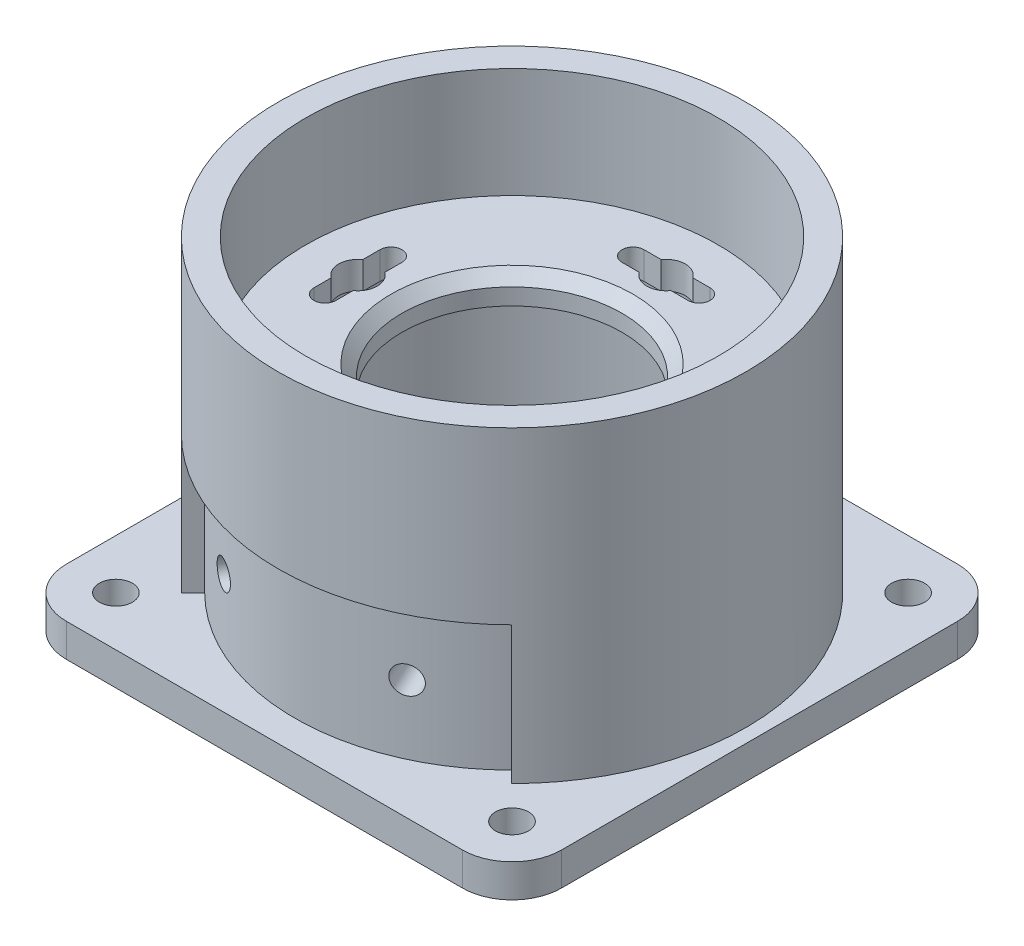
SolidWorks part; units mm, degrees
ref_plane "前视基准面" through (0, 0, 0) normal (0, 0, 1) x (1, 0, 0)
ref_plane "上视基准面" through (0, 0, 0) normal (0, 1, 0) x (1, 0, 0)
ref_plane "右视基准面" through (0, 0, 0) normal (1, 0, 0) x (0, 0, -1)
other "Configuration Table"
sketch "草图1" plane through (0, 0, 0) normal (0, 1, 0) x (1, 0, 0)
  line L0 (-27.9508, -25) -> (27.9508, -25)
  line L1 (-36, 45) -> (36, 45)
  line L2 (-45, 36) -> (-45, -36)
  line L3 (-36, -45) -> (36, -45)
  line L4 (45, 36) -> (45, -36)
  line L5 (-45, 45) -> (45, -45) construction
  line L6 (-45, -45) -> (45, 45) construction
  circle A0 centre (0, 0) radius 42.5
  circle A1 centre (0, 0) radius 37.5
  circle A2 centre (0, 0) radius 20
  arc A3 (36, 45) -> (45, 36) centre (36, 36) cw
  arc A4 (-45, -36) -> (-36, -45) centre (-36, -36) ccw
  arc A5 (-36, 45) -> (-45, 36) centre (-36, 36) ccw
  arc A6 (36, -45) -> (45, -36) centre (36, -36) ccw
  circle A7 centre (-36, 36) radius 3
  circle A8 centre (36, 36) radius 3
  circle A9 centre (36, -36) radius 3
  circle A10 centre (-36, -36) radius 3
  point P0 (0, 0)
  dimension "D2" = 85
  dimension "D3" = 5
  dimension "D4" = 40
  dimension "D5" = 9
  dimension "D6" = 6
  dimension "D1" = 90
  dimension "D7" = 25
extrude "凸台-拉伸1" add sketch "草图1" along normal blind 6 contours L3 A6 L4 A3 L1 A5 L2 A4 A0 region at (0, 0, -43.7272)
extrude "凸台-拉伸2" add sketch "草图1<3>" along normal blind 62 contours A0 A1 region at (-41.2979, 0, 0)
sketch "草图1<3>" plane through (0, 0, 0) normal (0, 1, 0) x (1, 0, 0) same geometry as "草图1"
extrude "凸台-拉伸3" add sketch "草图1<5>" against normal blind 5 from offset 42 contours A1 A2 | L0 A1 region at (-13.0325, 0, -34.1194) region at (0, 0, 30.0791)
sketch "草图1<5>" plane through (0, 0, 0) normal (0, 1, 0) x (1, 0, 0) same geometry as "草图1"
chamfer "倒角1" distance 2 angle 45 1 edges at (0, 42, 20)
extrude "凸台-拉伸4" add sketch "草图1<6>" along normal up to surface (37 mm away) contours L0 A1 region at (0, 0, 30.0791) up to face at (0, 37, 20)
sketch "草图1<6>" plane through (0, 0, 0) normal (0, 1, 0) x (1, 0, 0) same geometry as "草图1"
sketch "草图2" plane through (0, 6, 0) normal (0, 1, 0) x (1, 0, 0)
  line L0 (0, 0) -> (0, -48.9001) construction
  line L3 (-27.8824, -27.979) -> (-30, -30.104)
  line L4 (27.8824, -27.979) -> (30, -30.104)
  circle A0 centre (0, 0) radius 42.5 construction
  arc A1 (-30, -30.104) -> (30, -30.104) centre (0, 0) ccw
  circle A2 centre (0, 0) radius 39.5
  arc A3 (-27.8824, -27.979) -> (27.8824, -27.979) centre (0, 0) ccw
  dimension "D2" = 60
  dimension "D1" = 3
extrude "切除-拉伸2" cut sketch "草图2" along normal blind 25
ref_plane "基准面1" through (0, 18.5, 0) normal (0, 1, 0) x (1, 0, 0)
sketch "草图3" plane through (0, 18.5, 0) normal (0, 1, 0) x (1, 0, 0)
  line L0 (0, 0) -> (0, -53.2545) construction
  line L1 (0, 0) -> (-25.1722, -53.9819) construction
  line L2 (-11.6577, -25) -> (-17.0955, -22.4643)
  line L3 (-17.0955, -22.4643) -> (-18.9616, -26.4661)
  line L4 (-18.9616, -26.4661) -> (-15.7896, -27.9453)
  line L5 (-15.7896, -27.9453) -> (-20.1959, -37.3948)
  line L6 (-20.1959, -37.3948) -> (-17.9302, -38.4514)
  line L7 (-17.9302, -38.4514) -> (-11.6577, -25)
  line L8 (-27.9508, -25) -> (27.9508, -25) construction
  line L9 (17.9302, -38.4514) -> (11.6577, -25)
  line L10 (20.1959, -37.3948) -> (17.9302, -38.4514)
  line L11 (15.7896, -27.9453) -> (20.1959, -37.3948)
  line L12 (18.9616, -26.4661) -> (15.7896, -27.9453)
  line L13 (17.0955, -22.4643) -> (18.9616, -26.4661)
  line L14 (11.6577, -25) -> (17.0955, -22.4643)
  circle A0 centre (0, 0) radius 42.5 construction
  dimension "D1" = 12
  dimension "D2" = 2.5
  dimension "D3" = 32
  dimension "D4" = 25
revolve "切除-旋转1" cut sketch "草图3" angle 360 about L9 region at (16.0785, 18.5, 29.4354)
revolve "切除-旋转2" cut sketch "草图3<4>" angle 360 about L7 region at (-16.0785, 18.5, 29.4354)
sketch "草图3<4>" plane through (0, 18.5, 0) normal (0, 1, 0) x (1, 0, 0) same geometry as "草图3"
sketch "草图5" plane through (0, 42, 0) normal (0, 1, 0) x (1, 0, 0)
  line L0 (-6, 28) -> (6, 28) construction
  line L1 (-6, 30) -> (-2.8723, 30)
  line L2 (-6, 26) -> (-2.8723, 26)
  line L3 (2.8723, 30) -> (6, 30)
  line L4 (2.8723, 26) -> (6, 26)
  line L5 (26, 6) -> (26, 2.8723)
  line L6 (26, -2.8723) -> (26, -6)
  line L7 (30, -2.8723) -> (30, -6)
  line L8 (30, 6) -> (30, 2.8723)
  line L13 (-26, -6) -> (-26, -2.8723)
  line L14 (-26, 2.8723) -> (-26, 6)
  line L15 (-30, 2.8723) -> (-30, 6)
  line L16 (-30, -6) -> (-30, -2.8723)
  line L17 (-2.8723, -26) -> (-6, -26) [skipped]
  line L18 (6, -30) -> (2.8723, -30) [skipped]
  line L19 (-2.8723, -30) -> (-6, -30) [skipped]
  line L20 (6, -26) -> (2.8723, -26) [skipped]
  arc A0 (26.9244, -7.6861) -> (-26.9244, -7.6861) centre (0, 0) ccw construction
  arc A1 (-6, 30) -> (-6, 26) centre (-6, 28) ccw
  arc A2 (6, 26) -> (6, 30) centre (6, 28) ccw
  arc A3 (2.8723, 30) -> (-2.8723, 30) centre (0, 28) ccw
  arc A4 (26, 2.8723) -> (26, -2.8723) centre (28, 0) ccw
  arc A5 (-2.8723, 26) -> (2.8723, 26) centre (0, 28) ccw
  arc A6 (26, -6) -> (30, -6) centre (28, -6) ccw
  arc A7 (30, -2.8723) -> (30, 2.8723) centre (28, 0) ccw
  arc A8 (30, 6) -> (26, 6) centre (28, 6) ccw
  arc A13 (-26, -2.8723) -> (-26, 2.8723) centre (-28, 0) ccw
  arc A14 (-26, 6) -> (-30, 6) centre (-28, 6) ccw
  arc A15 (-30, 2.8723) -> (-30, -2.8723) centre (-28, 0) ccw
  arc A16 (-30, -6) -> (-26, -6) centre (-28, -6) ccw
  arc A17 (-2.8723, -30) -> (2.8723, -30) centre (0, -28) ccw [skipped]
  arc A18 (6, -30) -> (7.6861, -26.9244) centre (6, -28) ccw [skipped]
  arc A19 (2.8723, -26) -> (-2.8723, -26) centre (0, -28) ccw [skipped]
  arc A20 (-6, -26) -> (-6, -30) centre (-6, -28) ccw [skipped]
  point P5 (0, 28)
  point P51 (0, 0)
  dimension "D1" = 56
  dimension "D4" = 3.5
  dimension "D5" = 3.5
  dimension "D6" = 2
  dimension "D8" = 4
  dimension "D2" = 12
  dimension "D3" = 4
extrude "切除-拉伸3" cut sketch "草图5" against normal up to next
